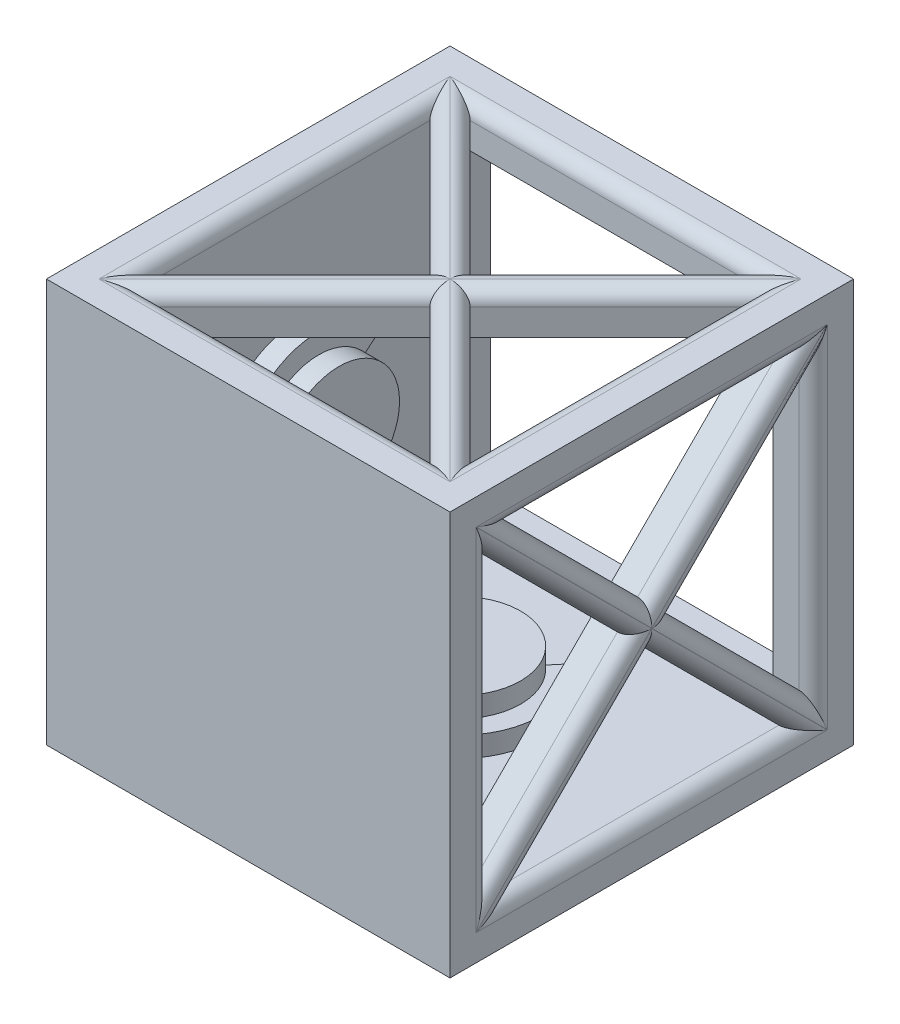
SolidWorks part; units mm, degrees
note: '?' marks a value the reader was unsure of.
ref_plane "Front Plane" through (0, 0, 0) normal (0, 0, 1) x (1, 0, 0)
ref_plane "Top Plane" through (0, 0, 0) normal (0, 1, 0) x (1, 0, 0)
ref_plane "Right Plane" through (0, 0, 0) normal (1, 0, 0) x (0, 0, -1)
sketch "Sketch1" plane through (0, 0, 0) normal (0, 1, 0) x (1, 0, 0)
  line L0 (36.4133, 74.7318) -> (36.4133, -25.2682)
  line L1 (36.4133, -25.2682) -> (-63.5867, -25.2682)
  line L2 (-63.5867, -25.2682) -> (-63.5867, 74.7318)
  line L3 (-63.5867, 74.7318) -> (36.4133, 74.7318)
extrude "Boss-Extrude1" add sketch "Sketch1" along normal blind 100
sketch "Sketch2" plane through (0, 100, 0) normal (0, 1, 0) x (1, 0, 0)
  line L3 (-53.5867, 64.7318) -> (26.4133, 64.7318)
  line L4 (26.4133, 64.7318) -> (26.4133, -15.2682)
  line L5 (26.4133, -15.2682) -> (-53.5867, -15.2682)
  line L6 (-53.5867, -15.2682) -> (-53.5867, 64.7318)
extrude "Cut-Extrude1" cut sketch "Sketch2" against normal blind 100
sketch "Sketch3" plane through (0, 0, 25.2682) normal (0, 0, 1) x (1, 0, 0)
  line L3 (-53.5867, 90) -> (26.4133, 90)
  line L4 (26.4133, 90) -> (26.4133, 10)
  line L5 (26.4133, 10) -> (-53.5867, 10)
  line L6 (-53.5867, 10) -> (-53.5867, 90)
extrude "Cut-Extrude2" cut sketch "Sketch3" against normal blind 100
sketch "Sketch4" plane through (-63.5867, 0, 0) normal (-1, 0, 0) x (0, 0, 1)
  line L3 (15.2682, 10) -> (-64.7318, 10)
  line L4 (-64.7318, 10) -> (-64.7318, 90)
  line L5 (-64.7318, 90) -> (15.2682, 90)
  line L6 (15.2682, 90) -> (15.2682, 10)
  line L14 (-64.7318, 85) -> (10.2682, 10)
  line L15 (15.2682, 15) -> (-59.7318, 90)
  line L17 (-64.7318, 15) -> (10.2682, 90)
  line L18 (15.2682, 85) -> (-59.7318, 10)
extrude "Cut-Extrude3" cut sketch "Sketch4" against normal blind 100
fillet "Fillet39" radius 3.505 8 edges at (-53.5867, 27.5, -42.2318) (-63.5867, 27.5, -42.2318) (-63.5867, 10, -24.7318) (-53.5867, 10, -24.7318) (-58.5867, 45, -24.7318) (-63.5867, 27.5, -7.2318) (-58.5867, 10, 10.2682) (-53.5867, 27.5, -7.2318)
fillet "Fillet40" radius 3.505 8 edges at (-53.5867, 72.5, -42.2318) (-63.5867, 72.5, -42.2318) (-63.5867, 72.5, -7.2318) (-53.5867, 72.5, -7.2318) (-58.5867, 90, -59.7318) (-63.5867, 90, -24.7318) (-58.5867, 90, 10.2682) (-53.5867, 90, -24.7318)
fillet "Fillet41" radius 3.505 8 edges at (-53.5867, 67.5, -2.2318) (-63.5867, 67.5, -2.2318) (-63.5867, 32.5, -2.2318) (-53.5867, 32.5, -2.2318) (-58.5867, 85, 15.2682) (-63.5867, 50, 15.2682) (-58.5867, 15, 15.2682) (-53.5867, 50, 15.2682)
fillet "Fillet42" radius 3.505 8 edges at (-53.5867, 50, -64.7318) (-63.5867, 50, -64.7318) (-63.5867, 32.5, -47.2318) (-53.5867, 32.5, -47.2318) (-58.5867, 85, -64.7318) (-63.5867, 67.5, -47.2318) (-58.5867, 50, -29.7318) (-53.5867, 67.5, -47.2318)
sketch "Sketch5" plane through (0, 10, 0) normal (0, 1, 0) x (1, 0, 0)
  line L0 (26.4133, -25.2682) -> (-53.5867, -25.2682)
  line L1 (-53.5867, -25.2682) -> (-53.5867, -20.2682)
  line L2 (-53.5867, -20.2682) -> (26.4133, -20.2682)
  line L3 (26.4133, -15.2682) -> (26.4133, -25.2682) construction
  line L4 (26.4133, -20.2682) -> (26.4133, -25.2682)
extrude "Boss-Extrude2" add sketch "Sketch5" along normal blind 80
sketch "Sketch9" plane through (0, 100, 0) normal (0, 1, 0) x (1, 0, 0)
  line L0 (26.4133, -15.0527) -> (26.4133, -10.0527)
  line L1 (26.4133, -15.2682) -> (26.4133, 64.7318) construction
  line L2 (26.4133, -15.0527) -> (21.4133, -15.0527)
  line L3 (26.4133, 59.7318) -> (26.4133, 64.7318)
  line L4 (26.4133, 64.7318) -> (21.4133, 64.7318)
  line L5 (26.4133, 64.7318) -> (-53.5867, 64.7318) construction
  line L6 (-53.5867, -15.2682) -> (-48.5867, -15.2682)
  line L7 (-53.5867, -15.2682) -> (26.4133, -15.2682) construction
  line L8 (-53.5867, -15.2682) -> (-53.5867, -10.2682)
  line L9 (-53.5867, 64.7318) -> (-53.5867, -15.2682) construction
  line L10 (-53.5867, -10.2682) -> (21.4133, 64.7318)
  line L11 (-48.5867, -15.2682) -> (26.4133, 59.7318)
  line L12 (-53.5867, 64.7318) -> (-48.5867, 64.7318)
  line L13 (-53.5867, 64.7318) -> (-53.5867, 59.7318)
  line L14 (-53.5867, 59.7318) -> (21.4133, -15.0527)
  line L15 (-48.5867, 64.7318) -> (26.4133, -10.0527)
  line M1 (26.4133, -15.2682) -> (-53.5867, -15.2682)
  line M2 (-53.5867, -15.2682) -> (-53.5867, 64.7318)
  line M3 (-53.5867, 64.7318) -> (26.4133, 64.7318)
  line M4 (26.4133, 64.7318) -> (26.4133, -15.2682)
extrude "Boss-Extrude4" add sketch "Sketch9" against normal blind 10 contours L15 L10 L14 L11 | L15 L14 L10 M3 M2 | L14 L10 L11 M2 M1 | L15 L11 L14 L2 M4 | L10 L15 L11 M4 M3
fillet "Fillet106" radius 3.505 1 edges at (-13.5867, 100, -64.7318)
fillet "Fillet107" radius 3.505 10 edges at (26.4133, 100, -24.8395) (5.691, 100, -49.0095) (-32.8191, 100, -49.0095) (-53.5867, 100, -24.7318) (-36.0615, 100, -42.257) (-36.0615, 100, -7.257) (-31.0579, 100, -2.2605) (3.9421, 100, -2.3683) (8.9421, 100, -42.2605) (8.9421, 100, -7.3683)
fillet "Fillet108" radius 3.505 1 edges at (-13.5651, 100, 15.2682)
ref_plane "Plane1" through (0, 50, 0) normal (0, 1, 0) x (1, 0, 0)
mirror "Mirror3" about plane through (0, 50, 0) normal (0, 1, 0) of "Boss-Extrude4"
fillet "Fillet109" radius 3.505 11 edges at (-11.0867, 0, 15.2682) (-13.5867, 0, -64.7318) (-53.5867, 0, -24.7318) (8.9421, 0, -42.2605) (-36.0615, 0, -42.257) (-31.0579, 0, -2.2605) (3.9421, 0, -2.3683) (8.9421, 0, -7.3683) (-36.0615, 0, -7.257) (-31.0615, 0, -47.257) (3.9385, 0, -47.257)
sketch "Sketch10" plane through (0, 0, 0) normal (0, -1, 0) x (-1, 0, 0)
  line L0 (-36.4133, -25.2682) -> (-36.4133, 74.7318)
  line L1 (-36.4133, 74.7318) -> (63.5867, 74.7318)
  line L2 (63.5867, 74.7318) -> (63.5867, -25.2682)
  line L3 (63.5867, -25.2682) -> (-36.4133, -25.2682)
extrude "Boss-Extrude6" add sketch "Sketch10" against normal blind 10
sketch "Sketch11" plane through (0, 100, 0) normal (0, 1, 0) x (1, 0, 0)
  line L1 (-63.5867, -25.2682) -> (36.4133, -25.2682)
  line L2 (-63.5867, -25.2682) -> (-63.5867, 74.7318)
  line L3 (-63.5867, 74.7318) -> (36.4133, 74.7318)
  line L4 (36.4133, -25.2682) -> (36.4133, 74.7318)
extrude "Boss-Extrude7" add sketch "Sketch11" against normal blind 10
sketch "Sketch12" plane through (0, 0, 20.2682) normal (0, 0, -1) x (-1, 0, 0)
  circle A0 centre (13.5867, 50) radius 15
extrude "Boss-Extrude8" add sketch "Sketch12" along normal blind 10
sketch "Sketch13" plane through (0, 0, 20.2682) normal (0, 0, -1) x (-1, 0, 0)
  line L0 (-0.5554, 64.1421) -> (2.9801, 60.6066)
  line L1 (2.9801, 39.3934) -> (-0.5554, 35.8579)
  line L2 (27.7288, 64.1421) -> (24.1933, 60.6066)
  line L3 (27.7288, 35.8579) -> (24.1933, 39.3934)
  arc A0 (-0.5554, 64.1421) -> (-0.5554, 35.8579) centre (13.5867, 50) ccw
  arc A1 (27.7288, 35.8579) -> (27.7288, 64.1421) centre (13.5867, 50) ccw
  arc A2 (2.9801, 60.6066) -> (2.9801, 39.3934) centre (13.5867, 50) ccw
  arc A3 (24.1933, 39.3934) -> (24.1933, 60.6066) centre (13.5867, 50) ccw
extrude "Boss-Extrude9" add sketch "Sketch13" along normal blind 5
sketch "Sketch18" plane through (0, 10, 0) normal (0, 1, 0) x (1, 0, 0)
  line L0 (-53.5867, 74.7318) -> (26.4133, -20.2682) construction
  line L1 (26.4133, -20.2682) -> (26.4133, 74.7318) construction
  line L2 (26.4133, 74.7318) -> (-53.5867, -20.2682) construction
  circle A0 centre (-13.5867, 27.2318) radius 15
extrude "Boss-Extrude10" add sketch "Sketch18" along normal blind 10
sketch "Sketch19" plane through (0, 10, 0) normal (0, 1, 0) x (1, 0, 0)
  line L0 (-53.5867, 74.7318) -> (-23.2487, 38.7054) construction
  line L1 (26.4133, -20.2682) -> (26.4133, 74.7318) construction
  line L2 (26.4133, 74.7318) -> (-3.9247, 38.7054) construction
  line L3 (-26.4694, 42.53) -> (-23.2487, 38.7054)
  line L4 (-26.4694, 11.9335) -> (-23.2487, 15.7581)
  line L5 (-3.9247, 15.7581) -> (26.4133, -20.2682) construction
  line L6 (-3.9247, 15.7581) -> (-0.704, 11.9335)
  line L7 (-23.2487, 15.7581) -> (-53.5867, -20.2682) construction
  line L8 (-3.9247, 38.7054) -> (-0.704, 42.53)
  arc A0 (-26.4694, 42.53) -> (-26.4694, 11.9335) centre (-13.5867, 27.2318) ccw
  arc A1 (-0.704, 11.9335) -> (-0.704, 42.53) centre (-13.5867, 27.2318) ccw
  arc A2 (-23.2487, 38.7054) -> (-23.2487, 15.7581) centre (-13.5867, 27.2318) ccw
  arc A3 (-3.9247, 15.7581) -> (-3.9247, 38.7054) centre (-13.5867, 27.2318) ccw
extrude "Boss-Extrude11" add sketch "Sketch19" along normal blind 5
sketch "Sketch22" plane through (0, 0, 20.2682) normal (0, 0, -1) x (-1, 0, 0)
  line L0 (53.5867, 10) -> (-26.4133, 90) construction
  line L1 (-26.4133, 90) -> (53.5867, 90) construction
  line L2 (53.5867, 90) -> (-26.4133, 10) construction
  point P9 (13.5867, 50)
ref_axis "Axis4" through (-13.5867, 50, 20.2682) along (0, 0, -1)?
sketch "Sketch25" plane through (0, 100, 0) normal (0, 1, 0) x (1, 0, 0)
  line L0 (-53.5867, 64.7318) -> (-53.5867, 59.7318)
  line L1 (-53.5867, -15.2682) -> (-53.5867, -10.2682)
  line L2 (-53.5867, 64.7318) -> (-53.5867, -15.2682)
  line L3 (-53.5867, -15.2682) -> (26.4133, -15.2682)
  line L4 (26.4133, -15.2682) -> (26.4133, 64.7318)
  line L5 (26.4133, 64.7318) -> (-53.5867, 64.7318)
  line L6 (26.4133, 59.7318) -> (26.4133, -10.2682)
  line L7 (26.4133, -15.2682) -> (21.4133, -15.2682)
  line L8 (26.4133, 64.7318) -> (21.4133, 64.7318)
  line L9 (26.4133, 59.7318) -> (-48.5867, -15.2682)
  line L10 (21.4133, 64.7318) -> (-53.5867, -10.2682)
  line L11 (-53.5867, 64.7318) -> (-48.5867, 64.7318)
  line L12 (-48.5867, -15.2682) -> (-53.5867, -15.2682)
  line L13 (26.4133, -10.2682) -> (-48.5867, 64.7318)
  line L14 (21.4133, -15.2682) -> (-53.5867, 59.7318)
extrude "Cut-Extrude4" cut sketch "Sketch25" against normal blind 10 contours L13 L4 L9 | L3 L14 L9 | L10 L14 L2 | L13 L10 L5
sketch "Sketch26" plane through (-63.5867, 0, 0) normal (-1, 0, 0) x (0, 0, 1)
  line L1 (-70.3057, 95.4321) -> (21.5353, 95.4321)
  line L2 (-70.3057, 95.4321) -> (-70.3057, 6.084)
  line L3 (-70.3057, 6.084) -> (21.5353, 6.084)
  line L4 (21.5353, 95.4321) -> (21.5353, 6.084)
extrude "Boss-Extrude12" add sketch "Sketch26" against normal blind 10
fillet "Fillet113" radius 3.505 1 edges at (26.4133, 100, -24.7318)
fillet "Fillet114" radius 3.505 12 edges at (36.4133, 10, -24.7318) (36.4133, 50, 15.2682) (36.4133, 67.5, -2.2318) (36.4133, 32.5, -2.2318) (36.4133, 27.5, -7.2318) (36.4133, 27.5, -42.2318) (36.4133, 32.5, -47.2318) (36.4133, 50, -64.7318) (36.4133, 67.5, -47.2318) (36.4133, 72.5, -7.2318) (36.4133, 72.5, -42.2318) (36.4133, 90, -24.7318)
sketch "Sketch28" plane through (-53.5867, 0, 0) normal (1, 0, 0) x (0, 0, -1)
  line L1 (-20.2682, 90) -> (-20.2682, 10)
  circle A0 centre (27.2318, 50) radius 15
extrude "Boss-Extrude13" add sketch "Sketch28" along normal blind 10 contours A0
sketch "Sketch29" plane through (-53.5867, 0, 0) normal (1, 0, 0) x (0, 0, -1)
  line L0 (38.7054, 59.662) -> (42.53, 62.8827)
  line L1 (38.7054, 40.338) -> (42.53, 37.1173)
  line L2 (15.7581, 59.662) -> (11.9335, 62.8827)
  line L3 (15.7581, 40.338) -> (11.9335, 37.1173)
  arc A0 (42.53, 62.8827) -> (11.9335, 62.8827) centre (27.2318, 50) ccw
  arc A1 (11.9335, 37.1173) -> (42.53, 37.1173) centre (27.2318, 50) ccw
  arc A2 (38.7054, 59.662) -> (15.7581, 59.662) centre (27.2318, 50) ccw
  arc A3 (15.7581, 40.338) -> (38.7054, 40.338) centre (27.2318, 50) ccw
extrude "Boss-Extrude14" add sketch "Sketch29" along normal blind 5
fillet "Fillet115" radius 3.505 11 edges at (-53.5867, 100, -24.7318) (-13.5867, 100, 15.2682) (-31.0867, 100, -2.2318) (3.9133, 100, -2.2318) (10.6658, 100, -5.4793) (10.6658, 100, -43.9843) (3.9133, 100, -47.2318) (-13.5867, 100, -64.7318) (-31.0867, 100, -47.2318) (-36.0867, 100, -42.2318) (-36.0867, 100, -7.2318)
